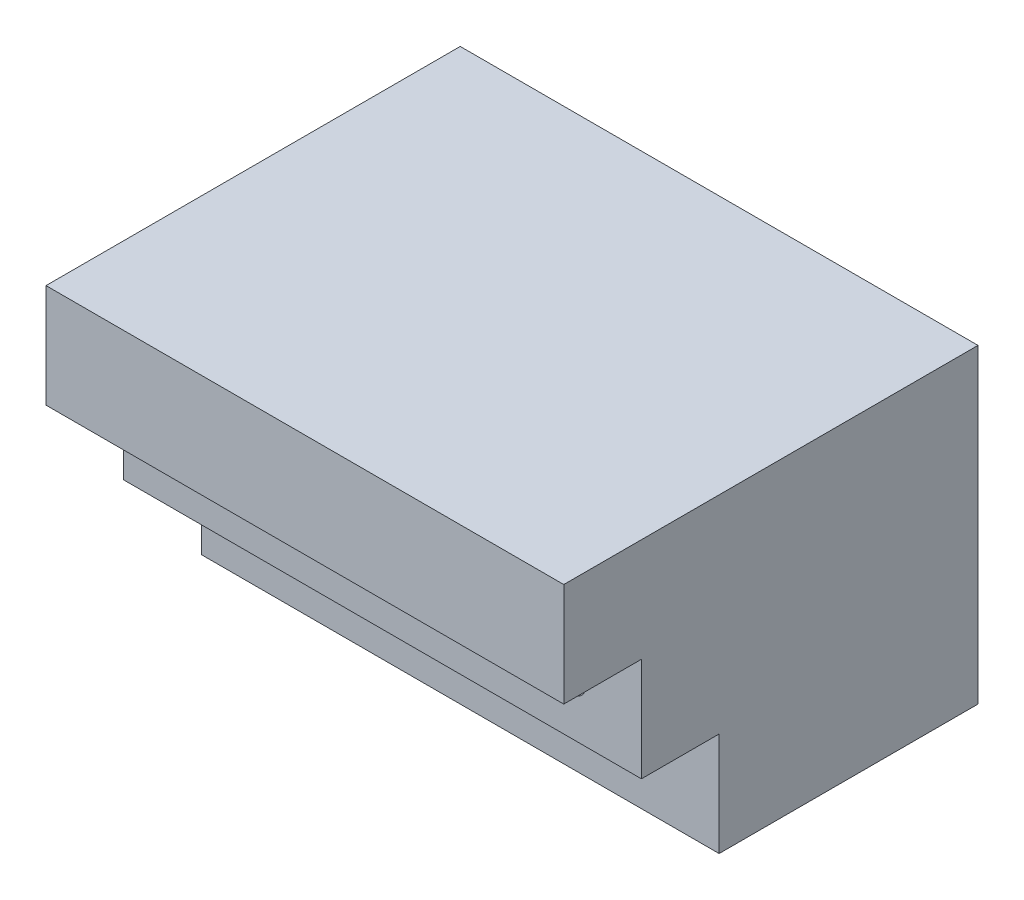
SolidWorks part; units mm, degrees
material "granite"
ref_plane "Front Plane" through (0, 0, 0) normal (0, 0, 1) x (1, 0, 0)
ref_plane "Top Plane" through (0, 0, 0) normal (0, 1, 0) x (1, 0, 0)
ref_plane "Right Plane" through (0, 0, 0) normal (1, 0, 0) x (0, 0, -1)
sketch "Эскиз1" plane through (0, 0, 0) normal (0, 0, 1) x (1, 0, 0)
  line L1 (0, 0) -> (200, 0)
  line L2 (0, 0) -> (0, 40)
  line L3 (0, 40) -> (200, 40)
  line L4 (200, 0) -> (200, 40)
  line L5 (0, 40) -> (200, 40)
  line L6 (0, 40) -> (0, 80)
  line L7 (0, 80) -> (200, 80)
  line L8 (200, 40) -> (200, 80)
extrude "Бобышка-Вытянуть1" add sketch "Эскиз1" along normal blind 100 contours L1 L4 L3 L2 region at (100, 20, 0)
extrude "Бобышка-Вытянуть2" add sketch "Эскиз1<3>" along normal blind 130 contours L3 L8 L7 L6 region at (100, 60, 0)
sketch "Эскиз1<3>" plane through (0, 0, 0) normal (0, 0, 1) x (1, 0, 0) same geometry as "Эскиз1"
sketch "Эскиз10" plane through (0, 0, 0) normal (0, 0, -1) x (-1, 0, 0)
  line L1 (0, 80) -> (-200, 80)
  line L2 (0, 80) -> (0, 120)
  line L3 (0, 120) -> (-200, 120)
  line L4 (-200, 80) -> (-200, 120)
extrude "Бобышка-Вытянуть3" add sketch "Эскиз10" against normal blind 160
sketch "Эскиз12" plane through (0, 0, 130) normal (0, 0, 1) x (1, 0, 0)
  line L0 (0, 60) -> (200, 60)
  line L1 (0, 40) -> (0, 80) construction
  line L2 (200, 40) -> (200, 80) construction
  circle A0 centre (100, 60) radius 5
  circle A1 centre (60.7405, 60) radius 5
  circle A2 centre (24.2205, 60) radius 5
  circle A3 centre (137.2383, 60) radius 5
  circle A4 centre (173.4258, 60) radius 5
extrude "Вырез-Вытянуть8" cut sketch "Эскиз12" against normal blind 50 draft 1 contours A2
extrude "Вырез-Вытянуть9" cut sketch "Эскиз12<5>" against normal blind 45 draft 1 contours A1
sketch "Эскиз12<5>" plane through (0, 0, 130) normal (0, 0, 1) x (1, 0, 0) same geometry as "Эскиз12"
extrude "Вырез-Вытянуть10" cut sketch "Эскиз12<6>" against normal blind 40 draft 1 contours A0
sketch "Эскиз12<6>" plane through (0, 0, 130) normal (0, 0, 1) x (1, 0, 0) same geometry as "Эскиз12"
extrude "Вырез-Вытянуть11" cut sketch "Эскиз12<7>" against normal blind 35 draft 1 contours A3
sketch "Эскиз12<7>" plane through (0, 0, 130) normal (0, 0, 1) x (1, 0, 0) same geometry as "Эскиз12"
extrude "Вырез-Вытянуть12" cut sketch "Эскиз12<8>" against normal blind 30 draft 1 contours A4
sketch "Эскиз12<8>" plane through (0, 0, 130) normal (0, 0, 1) x (1, 0, 0) same geometry as "Эскиз12"
